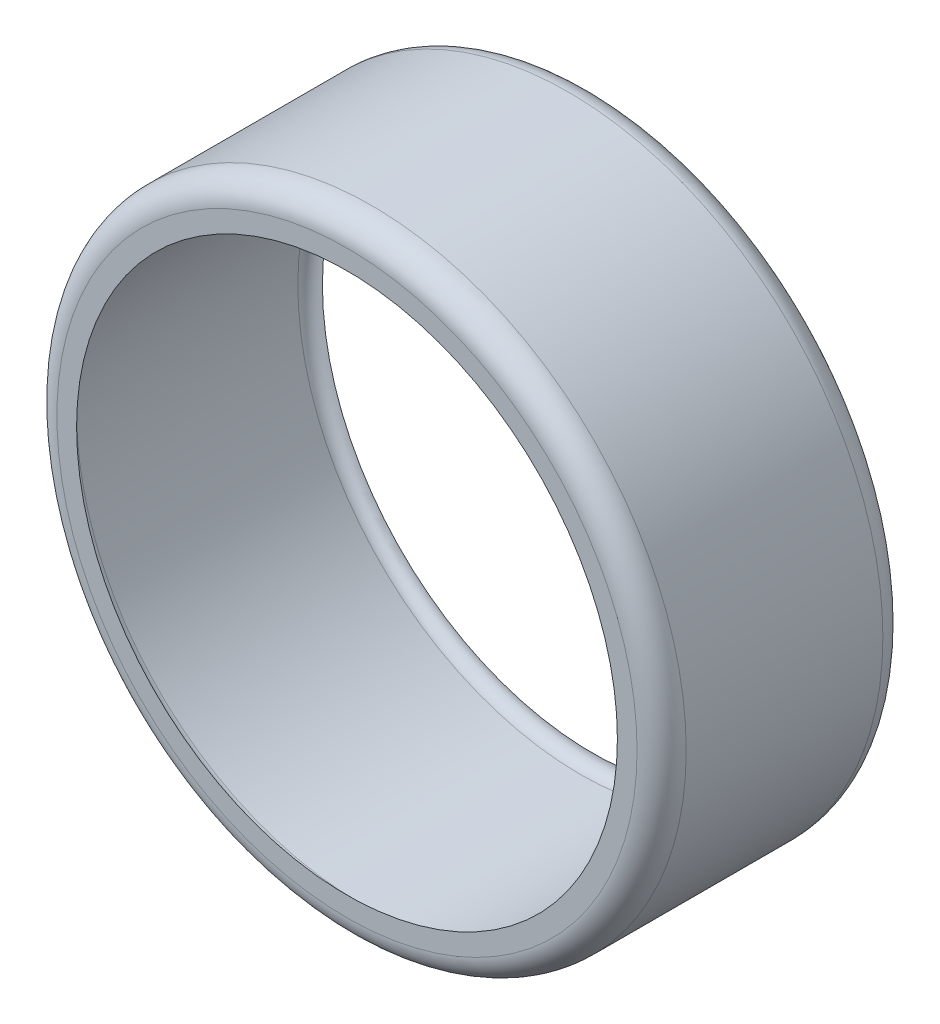
SolidWorks part; units mm, degrees
material "BUTYL"
ref_plane "Front Plane" through (0, 0, 0) normal (0, 0, 1) x (1, 0, 0)
ref_plane "Top Plane" through (0, 0, 0) normal (0, 1, 0) x (1, 0, 0)
ref_plane "Right Plane" through (0, 0, 0) normal (1, 0, 0) x (0, 0, -1)
sketch "Sketch1" plane through (0, 0, 0) normal (1, 0, 0) x (0, 0, -1)
  line L0 (0, 0) -> (14.4175, 0) construction
  line L1 (0, 27.94) -> (0, 29.972)
  line L2 (2.54, 32.512) -> (22.86, 32.512)
  line L3 (25.4, 29.972) -> (25.4, 27.94)
  line L4 (1.27, 29.21) -> (24.13, 29.21)
  arc A0 (0, 27.94) -> (1.27, 29.21) centre (1.27, 27.94) cw
  arc A1 (25.4, 27.94) -> (24.13, 29.21) centre (24.13, 27.94) ccw
  arc A2 (22.86, 32.512) -> (25.4, 29.972) centre (22.86, 29.972) cw
  arc A3 (2.54, 32.512) -> (0, 29.972) centre (2.54, 29.972) ccw
  dimension "D1" = 1.27
  dimension "D5" = 2.54
  dimension "D2" = 65.024
  dimension "D3" = 58.42
  dimension "D4" = 25.4
revolve "Revolve1" add sketch "Sketch1" angle 360 about L0
